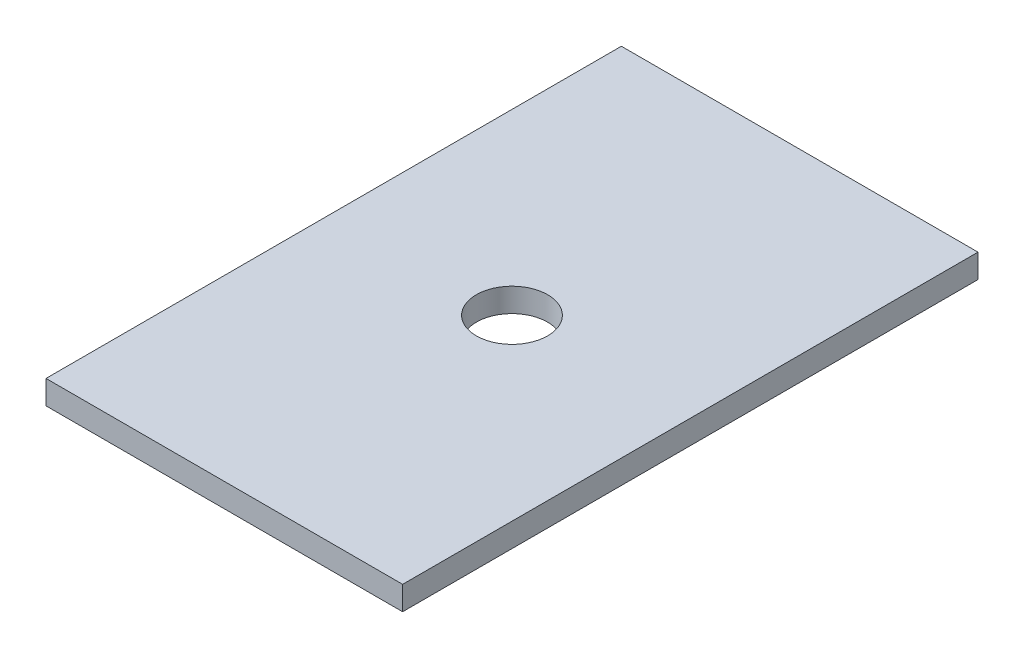
SolidWorks part; units mm, degrees
ref_plane "Front Plane" through (0, 0, 0) normal (0, 0, 1) x (1, 0, 0)
ref_plane "Top Plane" through (0, 0, 0) normal (0, 1, 0) x (1, 0, 0)
ref_plane "Right Plane" through (0, 0, 0) normal (1, 0, 0) x (0, 0, -1)
sketch "Sketch2" plane through (0, 0, 0) normal (0, 1, 0) x (1, 0, 0)
  line L1 (-75, -121) -> (75, -121)
  line L2 (-75, -121) -> (-75, 121)
  line L3 (-75, 121) -> (75, 121)
  line L4 (75, -121) -> (75, 121)
  line L5 (-75, -121) -> (75, 121) construction
  line L6 (-75, 121) -> (75, -121) construction
  circle A0 centre (0, 0) radius 15
  point P0 (0, 0)
  dimension "D2" = 30
  dimension "D1" = 242
extrude "Boss-Extrude3" add sketch "Sketch2" along normal blind 10
